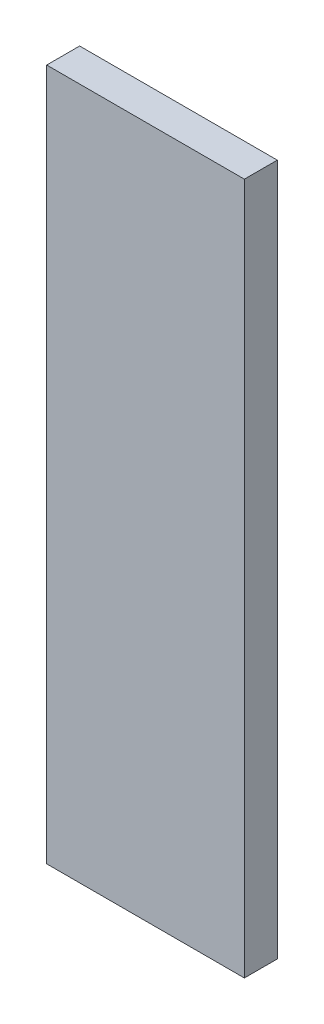
SolidWorks part; units mm, degrees
material "Простая углеродистая сталь"
ref_plane "Спереди" through (0, 0, 0) normal (0, 0, 1) x (1, 0, 0)
ref_plane "Сверху" through (0, 0, 0) normal (0, 1, 0) x (1, 0, 0)
ref_plane "Справа" through (0, 0, 0) normal (1, 0, 0) x (0, 0, -1)
sketch "Эскиз1" plane through (0, 0, 0) normal (0, 0, 1) x (1, 0, 0)
  line L1 (0, 0) -> (60, 0)
  line L2 (0, 0) -> (0, -210)
  line L3 (0, -210) -> (60, -210)
  line L4 (60, 0) -> (60, -210)
  dimension "D1" = 60
  dimension "D2" = 210
base flange "Базовая кромка1" sketch "Эскиз1" thickness 10 reverse thickness direction no parameters "D1"=3
sketch "Сгиб-Линии1" plane through (0, 0, 0) normal (0, 1, 0) x (1, 0, 0)
sketch "Граничная рамка1" plane through (0, 0, 0) normal (0, 1, 0) x (1, 0, 0)
sheet metal parameters "Листовой металл1" thickness 10 parameters "D1"=3
flat pattern "Развертка1" [suppressed]
sketch "Сгиб-Линии2" plane through (0, 0, 0) normal (0, 1, 0) x (1, 0, 0)
sketch "Граничная рамка2" [suppressed] plane through (0, 0, 0) normal (0, 1, 0) x (1, 0, 0)
